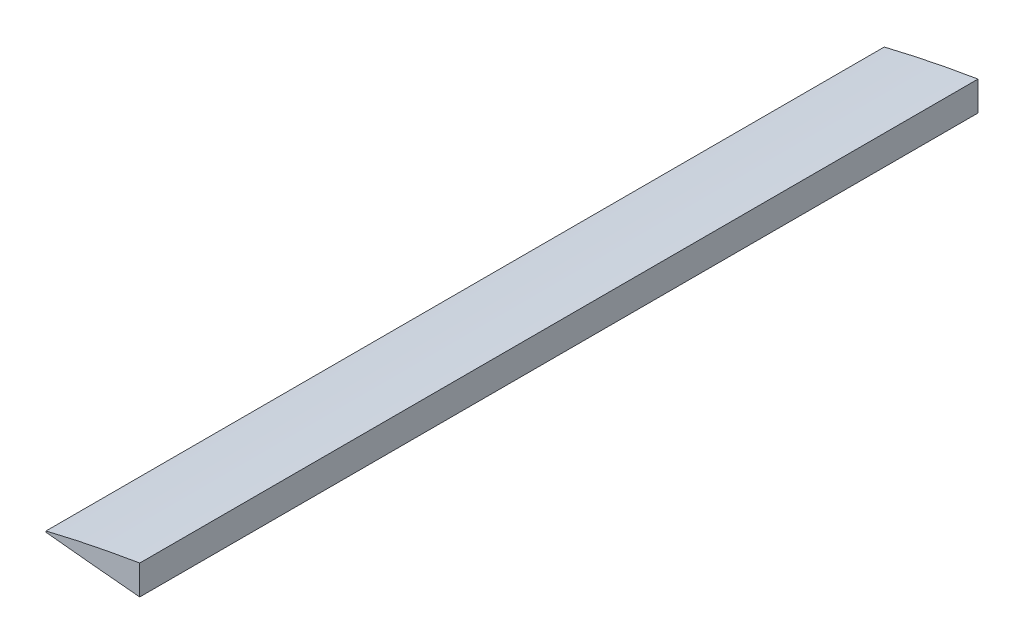
SolidWorks part; units mm, degrees
ref_plane "Front Plane" through (0, 0, 0) normal (0, 0, 1) x (1, 0, 0)
ref_plane "Top Plane" through (0, 0, 0) normal (0, 1, 0) x (1, 0, 0)
ref_plane "Right Plane" through (0, 0, 0) normal (1, 0, 0) x (0, 0, -1)
sketch "Sketch1" plane through (0, 0, 0) normal (0, 0, 1) x (1, 0, 0)
  line L0 (-194.7821, 14.3623) -> (-194.7821, -7.1181)
  line L1 (-263.219, 0.4204) -> (-263.219, -0.4137)
  spline S0 degree 3 poles (-194.7821, 14.3623) (-196.7808, 14.0308) (-201.6443, 13.2242) (-209.199, 11.8784) (-217.2748, 10.3785) (-224.8169, 8.9105) (-231.7807, 7.4997) (-238.1249, 6.1663) (-243.8123, 4.9313) (-248.8094, 3.8144) (-253.0872, 2.8341) (-256.6212, 2.0071) (-259.3909, 1.3478) (-261.3806, 0.8681) (-262.5698, 0.579) (-263.0945, 0.4508) (-263.219, 0.4204) knots 0 0 0 0 0.087007 0.211705 0.329527 0.439741 0.541661 0.634652 0.718135 0.791585 0.85454 0.906603 0.947445 0.976805 0.994497 1 1 1 1
  spline S1 degree 3 poles (-194.7821, -7.1181) (-196.5127, -6.9612) (-201.1128, -6.5442) (-208.4251, -5.8647) (-216.5467, -5.0997) (-224.1497, -4.3712) (-231.1857, -3.6866) (-237.6098, -3.0518) (-243.3806, -2.4732) (-248.4606, -1.956) (-252.817, -1.5081) (-256.4209, -1.1292) (-259.2495, -0.8392) (-261.2822, -0.6051) (-262.5095, -0.5063) (-263.063, -0.4131) (-263.2098, -0.4136) (-263.219, -0.4137) knots 0 0 0 0 0.075811 0.201508 0.320388 0.431695 0.534719 0.628797 0.713321 0.78774 0.851567 0.90438 0.945827 0.975633 0.993597 0.999599 1 1 1 1
extrude "Boss-Extrude1" add sketch "Sketch1" along normal blind 612
ref_plane "Plane1" through (0, 0, 83.9) normal (0, 0, 1) x (1, 0, 0)
sketch "Sketch2" plane through (0, 0, 83.9) normal (0, 0, 1) x (1, 0, 0)
  line L0 (-217.915, -7.698) -> (-196.915, -7.698)
  line L1 (-196.915, -7.698) -> (-196.915, 3.802)
  line L2 (-196.915, 3.802) -> (-217.915, 3.802)
  line L3 (-217.915, 3.802) -> (-217.915, -7.698)
extrude "Cut-Extrude1" cut sketch "Sketch2" along normal blind 13
